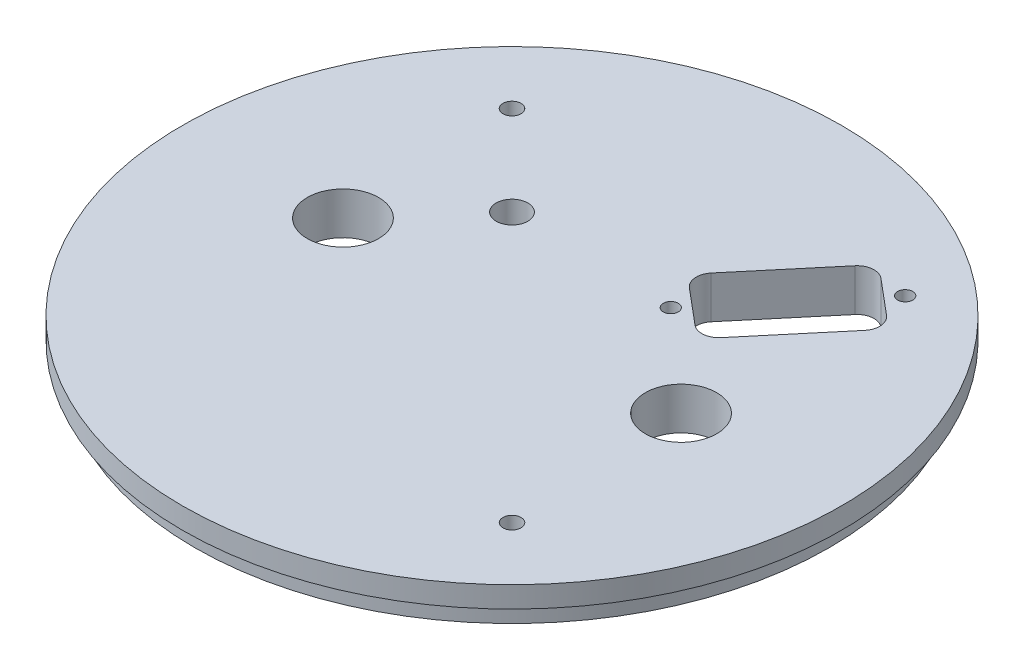
SolidWorks part; units mm, degrees
material "6061-T6 (SS)"
ref_plane "Front Plane" through (0, 0, 0) normal (0, 0, 1) x (1, 0, 0)
ref_plane "Top Plane" through (0, 0, 0) normal (0, 1, 0) x (1, 0, 0)
ref_plane "Right Plane" through (0, 0, 0) normal (1, 0, 0) x (0, 0, -1)
sketch "Sketch1" plane through (0, 0, 0) normal (0, 1, 0) x (1, 0, 0)
  line L0 (0, -49.5173) -> (0, 49.5173) construction
  line L1 (-49.5173, 0) -> (49.5173, 0) construction
  line L2 (-26.9408, 26.9408) -> (0, 0) construction
  line L3 (0, 56.7387) -> (0, 29.6936) construction
  line L4 (3.6407, 56.7387) -> (3.6407, 29.6936) construction
  line L5 (-3.6407, 56.7387) -> (-3.6407, 29.6936) construction
  line L6 (0, -56.7387) -> (0, -29.6936) construction
  line L7 (3.6407, -56.7387) -> (3.6407, -29.6936) construction
  line L8 (-3.6407, -56.7387) -> (-3.6407, -29.6936) construction
  line L9 (-35.014, -35.014) -> (54.3236, 54.3236) construction
  circle A0 centre (0, 0) radius 49.5173
  circle A1 centre (0, 0) radius 3.175 construction
  circle A2 centre (25.4, 0) radius 5.3578
  circle A3 centre (-25.4, 0) radius 5.3578
  circle A4 centre (-26.9408, 26.9408) radius 1.3589
  arc A6 (3.6407, 56.7387) -> (-3.6407, 56.7387) centre (0, 56.7387) ccw construction
  arc A7 (-3.6407, 29.6936) -> (3.6407, 29.6936) centre (0, 29.6936) ccw construction
  arc A8 (3.6407, -56.7387) -> (-3.6407, -56.7387) centre (0, -56.7387) cw construction
  arc A9 (-3.6407, -29.6936) -> (3.6407, -29.6936) centre (0, -29.6936) cw construction
  circle A10 centre (26.9408, -26.9408) radius 1.3589
  circle A11 centre (-13.4704, 13.4704) radius 2.3813
  circle A12 centre (13.4704, -13.4704) radius 2.3813 construction
  point P16 (0, 43.2162)
  point P19 (0, 0)
  point P26 (0, -43.2162)
  dimension "D1" = 99.0346
  dimension "D2" = 6.35
  dimension "D3" = 10.7156
  dimension "D5" = 2.7178
  dimension "D8" = 4.7625
  dimension "D6" = 38.1
  dimension "D7" = 45
  dimension "D4" = 45
  dimension "D9" = 25.4
extrude "Boss-Extrude1" add sketch "Sketch1" along normal blind 6.35
sketch "Sketch2" plane through (0, 0, 0) normal (0, -1, 0) x (1, 0, 0)
  circle A0 centre (0, 0) radius 49.5173
  circle A1 centre (0, 0) radius 47.6885
  dimension "D1" = 99.0346
  dimension "D2" = 95.377
extrude "Cut-Extrude1" cut sketch "Sketch2" against normal blind 3.175
sketch "Sketch3" plane through (0, 6.35, 0) normal (0, 1, 0) x (1, 0, 0)
  line L0 (0, 49.5173) -> (0, -49.5173) construction
  line L1 (-49.5173, 0) -> (49.5173, 0) construction
  line L2 (0, 34.925) -> (0, 13.335) construction
  line L3 (3.2385, 34.925) -> (3.2385, 13.335)
  line L4 (-3.2385, 34.925) -> (-3.2385, 13.335)
  line L5 (0, -34.925) -> (0, -13.335) construction
  line L6 (3.2385, -34.925) -> (3.2385, -13.335)
  line L7 (-3.2385, -34.925) -> (-3.2385, -13.335)
  circle A0 centre (0, 0) radius 49.5173 construction
  arc A1 (3.2385, 34.925) -> (-3.2385, 34.925) centre (0, 34.925) ccw
  arc A2 (-3.2385, 13.335) -> (3.2385, 13.335) centre (0, 13.335) ccw
  arc A3 (3.2385, -34.925) -> (-3.2385, -34.925) centre (0, -34.925) cw
  arc A4 (-3.2385, -13.335) -> (3.2385, -13.335) centre (0, -13.335) cw
  point P7 (0, 13.335)
  point P8 (0, 34.925)
  point P12 (0, 24.13)
  point P20 (0, -24.13)
  point P25 (0, -34.925)
  point P26 (0, -13.335)
  dimension "D1" = 13.335
  dimension "D2" = 34.925
  dimension "D3" = 6.477
extrude "Cut-Extrude2" cut sketch "Sketch3" against normal blind 3.556 from offset 5.969 offset against normal yes
hole_wizard "Tap Drill for #4-40 Tap1" positions "Sketch5" profile "Sketch6" hole size "#4-40" standard "ANSI Inch" end condition through all
sketch "Sketch5" plane through (0, 6.35, 0) normal (0, 1, 0) x (1, 0, 0)
  line L0 (0, 0) -> (53.6567, 63.9455) construction
  line L2 (0, 0) -> (25.4, 0) construction
  point P0 (10.8845, 12.9717)
  point P2 (26.9542, 32.1228)
  dimension "D1" = 50
  dimension "D2" = 25
  dimension "D3" = 16.9333
sketch "Sketch6" plane through (10.8845, 6.35, -12.9717) normal (1, 0, 0) x (0, 0, 1)
  line L0 (0, 0) -> (0, 6.35)
  line L1 (0, 6.35) -> (1.1303, 6.35)
  line L2 (1.1303, 6.35) -> (1.1303, 0)
  line L5 (1.1303, 0) -> (0, 0)
  line L11 (0, -6.35) -> (0, 107.95) construction
  dimension "Thru Hole Dia." = 2.2606
  dimension "Thru Hole Depth" = 6.35
sketch "Sketch4" plane through (0, 6.35, 0) normal (0, 1, 0) x (1, 0, 0)
  line L0 (9.7272, 16.927) -> (14.9807, 12.5187)
  line L1 (9.4141, 20.5054) -> (19.2796, 32.2627)
  line L2 (18.5591, 12.8318) -> (28.4247, 24.5891)
  line L3 (22.858, 32.5757) -> (28.1116, 28.1675)
  line L4 (0, 0) -> (26.9542, 32.1228) construction
  circle A1 centre (10.8845, 12.9717) radius 1.1303 construction
  arc A2 (19.2796, 32.2627) -> (22.858, 32.5757) centre (21.2254, 30.63) cw
  arc A3 (28.4247, 24.5891) -> (28.1116, 28.1675) centre (26.4789, 26.2217) ccw
  arc A4 (14.9807, 12.5187) -> (18.5591, 12.8318) centre (16.6134, 14.4645) ccw
  arc A5 (9.4141, 20.5054) -> (9.7272, 16.927) centre (11.3599, 18.8727) ccw
  point P11 (12.3539, 14.7229)
  dimension "D4" = 2.54
  dimension "D1" = 2.286
  dimension "D2" = 2.286
  dimension "D3" = 11.938
extrude "Cut-Extrude3" cut sketch "Sketch4" against normal through all
equation "\"leadDist\"= \"Lead_Screw_Dist\""
equation "\"Lead_Screw_Dist\" = 2in"
equation "\"D9@Sketch1\"=\"Lead_Screw_Dist\"/2"
equation "\"Lead_Screw_Diam\" = 0.375in"
equation "\"D3@Sketch1\"=\"Lead_Screw_Hole_Diam\""
equation "\"DB9_Hole_Dist\"= 25mm"
equation "\"Airbrakes_Wire_Hole_Dia\"= .25in"
equation "\"Mid_Coupler_Length\"= 13in"
equation "\"D2@Sketch5\"=\"DB9_Hole_Dist\""
equation "\"DB9_Relief_Width\"= 0.47in"
equation "\"DB9_Relief_Hole_Offset\"= 0.09in"
equation "\"D1@Sketch4\"=\"DB9_Relief_Hole_Offset\""
equation "\"D2@Sketch4\"=\"DB9_Relief_Hole_Offset\""
equation "\"D3@Sketch4\"=\"DB9_Relief_Width\""
equation "\"Body_Tube_OD\"= 4.024in"
equation "\"Body_Tube_ID\"= 3.90in"
equation "\"Coupler_OD\" = 3.899in"
equation "\"Coupler_ID\" = 3.755in"
equation "\"Avionics_Bulkhead_Thickness\" = 0.25in"
equation "\"Avionics_Bulkhead_Lip\" = 0.125in"
equation "\"Lead_Screw_Hole_Diam\" = (27/64)*1in"
equation "\"Lead_Screw_Length\" = \"Mid_Coupler_Length\" + 2*0.375in + 2*0.5in"
equation "\"D1@Sketch1\"=\"Coupler_OD\""
equation "\"D1@Sketch2\"=\"Coupler_OD\""
equation "\"D1@Cut-Extrude1\"=\"Avionics_Bulkhead_Lip\""
equation "\"D1@Boss-Extrude1\"=\"Avionics_Bulkhead_Thickness\""
equation "\"D2@Sketch2\"=\"Coupler_ID\""
